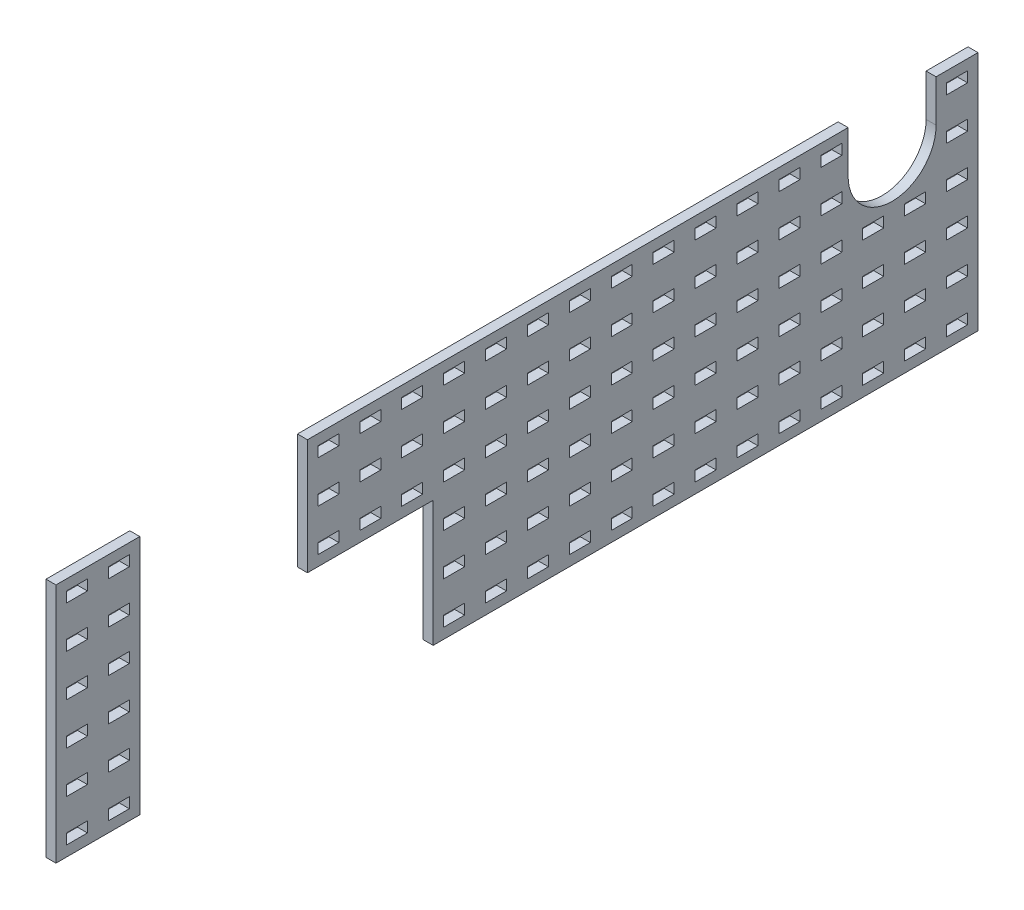
SolidWorks part; units mm, degrees
ref_plane "Front Plane" through (0, 0, 0) normal (0, 0, 1) x (1, 0, 0)
ref_plane "Top Plane" through (0, 0, 0) normal (0, 1, 0) x (1, 0, 0)
ref_plane "Right Plane" through (0, 0, 0) normal (1, 0, 0) x (0, 0, -1)
sketch "Sketch1" plane through (0, 0, 0) normal (1, 0, 0) x (0, 0, -1)
  line L1 (-279.4, -73.025) -> (279.4, -73.025)
  line L2 (-279.4, -73.025) -> (-279.4, 73.025)
  line L3 (-279.4, 73.025) -> (279.4, 73.025)
  line L4 (279.4, -73.025) -> (279.4, 73.025)
  line L5 (-279.4, -73.025) -> (279.4, 73.025) construction
  line L6 (-279.4, 73.025) -> (279.4, -73.025) construction
  point P0 (0, 0)
  dimension "D1" = 558.8
  dimension "D2" = 146.05
extrude "Boss-Extrude1" add sketch "Sketch1" along normal mid plane 6.0452
sketch "Sketch2" plane through (3.0226, 0, 0) normal (1, 0, 0) x (0, 0, -1)
  line L0 (-279.4, -73.025) -> (279.4, -73.025) construction
  line L1 (260.35, -60.325) -> (273.05, -60.325)
  line L2 (260.35, -60.325) -> (260.35, -66.675)
  line L3 (260.35, -66.675) -> (273.05, -66.675)
  line L4 (273.05, -60.325) -> (273.05, -66.675)
  line L5 (260.35, -60.325) -> (273.05, -66.675) construction
  line L6 (260.35, -66.675) -> (273.05, -60.325) construction
  line L7 (279.4, -73.025) -> (279.4, 73.025) construction
  line L8 (234.95, -66.675) -> (247.65, -66.675)
  line L9 (234.95, -60.325) -> (234.95, -66.675)
  line L10 (234.95, -60.325) -> (247.65, -60.325)
  line L11 (247.65, -60.325) -> (247.65, -66.675)
  line L12 (209.55, -66.675) -> (222.25, -66.675)
  line L13 (209.55, -60.325) -> (209.55, -66.675)
  line L14 (209.55, -60.325) -> (222.25, -60.325)
  line L15 (222.25, -60.325) -> (222.25, -66.675)
  line L16 (184.15, -66.675) -> (196.85, -66.675)
  line L17 (184.15, -60.325) -> (184.15, -66.675)
  line L18 (184.15, -60.325) -> (196.85, -60.325)
  line L19 (196.85, -60.325) -> (196.85, -66.675)
  line L20 (158.75, -66.675) -> (171.45, -66.675)
  line L21 (158.75, -60.325) -> (158.75, -66.675)
  line L22 (158.75, -60.325) -> (171.45, -60.325)
  line L23 (171.45, -60.325) -> (171.45, -66.675)
  line L24 (133.35, -66.675) -> (146.05, -66.675)
  line L25 (133.35, -60.325) -> (133.35, -66.675)
  line L26 (133.35, -60.325) -> (146.05, -60.325)
  line L27 (146.05, -60.325) -> (146.05, -66.675)
  line L28 (107.95, -66.675) -> (120.65, -66.675)
  line L29 (107.95, -60.325) -> (107.95, -66.675)
  line L30 (107.95, -60.325) -> (120.65, -60.325)
  line L31 (120.65, -60.325) -> (120.65, -66.675)
  line L32 (82.55, -66.675) -> (95.25, -66.675)
  line L33 (82.55, -60.325) -> (82.55, -66.675)
  line L34 (82.55, -60.325) -> (95.25, -60.325)
  line L35 (95.25, -60.325) -> (95.25, -66.675)
  line L36 (57.15, -66.675) -> (69.85, -66.675)
  line L37 (57.15, -60.325) -> (57.15, -66.675)
  line L38 (57.15, -60.325) -> (69.85, -60.325)
  line L39 (69.85, -60.325) -> (69.85, -66.675)
  line L40 (31.75, -66.675) -> (44.45, -66.675)
  line L41 (31.75, -60.325) -> (31.75, -66.675)
  line L42 (31.75, -60.325) -> (44.45, -60.325)
  line L43 (44.45, -60.325) -> (44.45, -66.675)
  line L44 (6.35, -66.675) -> (19.05, -66.675)
  line L45 (6.35, -60.325) -> (6.35, -66.675)
  line L46 (6.35, -60.325) -> (19.05, -60.325)
  line L47 (19.05, -60.325) -> (19.05, -66.675)
  line L48 (-19.05, -66.675) -> (-6.35, -66.675)
  line L49 (-19.05, -60.325) -> (-19.05, -66.675)
  line L50 (-19.05, -60.325) -> (-6.35, -60.325)
  line L51 (-6.35, -60.325) -> (-6.35, -66.675)
  line L52 (-44.45, -66.675) -> (-31.75, -66.675)
  line L53 (-44.45, -60.325) -> (-44.45, -66.675)
  line L54 (-44.45, -60.325) -> (-31.75, -60.325)
  line L55 (-31.75, -60.325) -> (-31.75, -66.675)
  line L56 (-69.85, -66.675) -> (-57.15, -66.675)
  line L57 (-69.85, -60.325) -> (-69.85, -66.675)
  line L58 (-69.85, -60.325) -> (-57.15, -60.325)
  line L59 (-57.15, -60.325) -> (-57.15, -66.675)
  line L60 (-95.25, -66.675) -> (-82.55, -66.675)
  line L61 (-95.25, -60.325) -> (-95.25, -66.675)
  line L62 (-95.25, -60.325) -> (-82.55, -60.325)
  line L63 (-82.55, -60.325) -> (-82.55, -66.675)
  line L64 (-120.65, -66.675) -> (-107.95, -66.675)
  line L65 (-120.65, -60.325) -> (-120.65, -66.675)
  line L66 (-120.65, -60.325) -> (-107.95, -60.325)
  line L67 (-107.95, -60.325) -> (-107.95, -66.675)
  line L68 (-146.05, -66.675) -> (-133.35, -66.675)
  line L69 (-146.05, -60.325) -> (-146.05, -66.675)
  line L70 (-146.05, -60.325) -> (-133.35, -60.325)
  line L71 (-133.35, -60.325) -> (-133.35, -66.675)
  line L72 (-171.45, -66.675) -> (-158.75, -66.675)
  line L73 (-171.45, -60.325) -> (-171.45, -66.675)
  line L74 (-171.45, -60.325) -> (-158.75, -60.325)
  line L75 (-158.75, -60.325) -> (-158.75, -66.675)
  line L76 (-196.85, -66.675) -> (-184.15, -66.675)
  line L77 (-196.85, -60.325) -> (-196.85, -66.675)
  line L78 (-196.85, -60.325) -> (-184.15, -60.325)
  line L79 (-184.15, -60.325) -> (-184.15, -66.675)
  line L80 (-222.25, -66.675) -> (-209.55, -66.675)
  line L81 (-222.25, -60.325) -> (-222.25, -66.675)
  line L82 (-222.25, -60.325) -> (-209.55, -60.325)
  line L83 (-209.55, -60.325) -> (-209.55, -66.675)
  line L84 (-247.65, -66.675) -> (-234.95, -66.675)
  line L85 (-247.65, -60.325) -> (-247.65, -66.675)
  line L86 (-247.65, -60.325) -> (-234.95, -60.325)
  line L87 (-234.95, -60.325) -> (-234.95, -66.675)
  line L88 (-273.05, -66.675) -> (-260.35, -66.675)
  line L89 (-273.05, -60.325) -> (-273.05, -66.675)
  line L90 (-273.05, -60.325) -> (-260.35, -60.325)
  line L91 (-260.35, -60.325) -> (-260.35, -66.675)
  line L92 (234.95, -41.275) -> (247.65, -41.275)
  line L93 (234.95, -34.925) -> (234.95, -41.275)
  line L94 (234.95, -34.925) -> (247.65, -34.925)
  line L95 (247.65, -34.925) -> (247.65, -41.275)
  line L96 (209.55, -41.275) -> (222.25, -41.275)
  line L97 (209.55, -34.925) -> (209.55, -41.275)
  line L98 (209.55, -34.925) -> (222.25, -34.925)
  line L99 (222.25, -34.925) -> (222.25, -41.275)
  line L100 (184.15, -41.275) -> (196.85, -41.275)
  line L101 (184.15, -34.925) -> (184.15, -41.275)
  line L102 (184.15, -34.925) -> (196.85, -34.925)
  line L103 (196.85, -34.925) -> (196.85, -41.275)
  line L104 (158.75, -41.275) -> (171.45, -41.275)
  line L105 (158.75, -34.925) -> (158.75, -41.275)
  line L106 (158.75, -34.925) -> (171.45, -34.925)
  line L107 (171.45, -34.925) -> (171.45, -41.275)
  line L108 (133.35, -41.275) -> (146.05, -41.275)
  line L109 (133.35, -34.925) -> (133.35, -41.275)
  line L110 (133.35, -34.925) -> (146.05, -34.925)
  line L111 (146.05, -34.925) -> (146.05, -41.275)
  line L112 (107.95, -41.275) -> (120.65, -41.275)
  line L113 (107.95, -34.925) -> (107.95, -41.275)
  line L114 (107.95, -34.925) -> (120.65, -34.925)
  line L115 (120.65, -34.925) -> (120.65, -41.275)
  line L116 (82.55, -41.275) -> (95.25, -41.275)
  line L117 (82.55, -34.925) -> (82.55, -41.275)
  line L118 (82.55, -34.925) -> (95.25, -34.925)
  line L119 (95.25, -34.925) -> (95.25, -41.275)
  line L120 (57.15, -41.275) -> (69.85, -41.275)
  line L121 (57.15, -34.925) -> (57.15, -41.275)
  line L122 (57.15, -34.925) -> (69.85, -34.925)
  line L123 (69.85, -34.925) -> (69.85, -41.275)
  line L124 (31.75, -41.275) -> (44.45, -41.275)
  line L125 (31.75, -34.925) -> (31.75, -41.275)
  line L126 (31.75, -34.925) -> (44.45, -34.925)
  line L127 (44.45, -34.925) -> (44.45, -41.275)
  line L128 (6.35, -41.275) -> (19.05, -41.275)
  line L129 (6.35, -34.925) -> (6.35, -41.275)
  line L130 (6.35, -34.925) -> (19.05, -34.925)
  line L131 (19.05, -34.925) -> (19.05, -41.275)
  line L132 (-19.05, -41.275) -> (-6.35, -41.275)
  line L133 (-19.05, -34.925) -> (-19.05, -41.275)
  line L134 (-19.05, -34.925) -> (-6.35, -34.925)
  line L135 (-6.35, -34.925) -> (-6.35, -41.275)
  line L136 (-44.45, -41.275) -> (-31.75, -41.275)
  line L137 (-44.45, -34.925) -> (-44.45, -41.275)
  line L138 (-44.45, -34.925) -> (-31.75, -34.925)
  line L139 (-31.75, -34.925) -> (-31.75, -41.275)
  line L140 (-69.85, -41.275) -> (-57.15, -41.275)
  line L141 (-69.85, -34.925) -> (-69.85, -41.275)
  line L142 (-69.85, -34.925) -> (-57.15, -34.925)
  line L143 (-57.15, -34.925) -> (-57.15, -41.275)
  line L144 (-95.25, -41.275) -> (-82.55, -41.275)
  line L145 (-95.25, -34.925) -> (-95.25, -41.275)
  line L146 (-95.25, -34.925) -> (-82.55, -34.925)
  line L147 (-82.55, -34.925) -> (-82.55, -41.275)
  line L148 (-120.65, -41.275) -> (-107.95, -41.275)
  line L149 (-120.65, -34.925) -> (-120.65, -41.275)
  line L150 (-120.65, -34.925) -> (-107.95, -34.925)
  line L151 (-107.95, -34.925) -> (-107.95, -41.275)
  line L152 (-146.05, -41.275) -> (-133.35, -41.275)
  line L153 (-146.05, -34.925) -> (-146.05, -41.275)
  line L154 (-146.05, -34.925) -> (-133.35, -34.925)
  line L155 (-133.35, -34.925) -> (-133.35, -41.275)
  line L156 (-171.45, -41.275) -> (-158.75, -41.275)
  line L157 (-171.45, -34.925) -> (-171.45, -41.275)
  line L158 (-171.45, -34.925) -> (-158.75, -34.925)
  line L159 (-158.75, -34.925) -> (-158.75, -41.275)
  line L160 (-196.85, -41.275) -> (-184.15, -41.275)
  line L161 (-196.85, -34.925) -> (-196.85, -41.275)
  line L162 (-196.85, -34.925) -> (-184.15, -34.925)
  line L163 (-184.15, -34.925) -> (-184.15, -41.275)
  line L164 (-222.25, -41.275) -> (-209.55, -41.275)
  line L165 (-222.25, -34.925) -> (-222.25, -41.275)
  line L166 (-222.25, -34.925) -> (-209.55, -34.925)
  line L167 (-209.55, -34.925) -> (-209.55, -41.275)
  line L168 (-247.65, -41.275) -> (-234.95, -41.275)
  line L169 (-247.65, -34.925) -> (-247.65, -41.275)
  line L170 (-247.65, -34.925) -> (-234.95, -34.925)
  line L171 (-234.95, -34.925) -> (-234.95, -41.275)
  line L172 (-273.05, -41.275) -> (-260.35, -41.275)
  line L173 (-273.05, -34.925) -> (-273.05, -41.275)
  line L174 (-273.05, -34.925) -> (-260.35, -34.925)
  line L175 (-260.35, -34.925) -> (-260.35, -41.275)
  line L176 (234.95, -15.875) -> (247.65, -15.875)
  line L177 (234.95, -9.525) -> (234.95, -15.875)
  line L178 (234.95, -9.525) -> (247.65, -9.525)
  line L179 (247.65, -9.525) -> (247.65, -15.875)
  line L180 (209.55, -15.875) -> (222.25, -15.875)
  line L181 (209.55, -9.525) -> (209.55, -15.875)
  line L182 (209.55, -9.525) -> (222.25, -9.525)
  line L183 (222.25, -9.525) -> (222.25, -15.875)
  line L184 (184.15, -15.875) -> (196.85, -15.875)
  line L185 (184.15, -9.525) -> (184.15, -15.875)
  line L186 (184.15, -9.525) -> (196.85, -9.525)
  line L187 (196.85, -9.525) -> (196.85, -15.875)
  line L188 (158.75, -15.875) -> (171.45, -15.875)
  line L189 (158.75, -9.525) -> (158.75, -15.875)
  line L190 (158.75, -9.525) -> (171.45, -9.525)
  line L191 (171.45, -9.525) -> (171.45, -15.875)
  line L192 (133.35, -15.875) -> (146.05, -15.875)
  line L193 (133.35, -9.525) -> (133.35, -15.875)
  line L194 (133.35, -9.525) -> (146.05, -9.525)
  line L195 (146.05, -9.525) -> (146.05, -15.875)
  line L196 (107.95, -15.875) -> (120.65, -15.875)
  line L197 (107.95, -9.525) -> (107.95, -15.875)
  line L198 (107.95, -9.525) -> (120.65, -9.525)
  line L199 (120.65, -9.525) -> (120.65, -15.875)
  line L200 (82.55, -15.875) -> (95.25, -15.875)
  line L201 (82.55, -9.525) -> (82.55, -15.875)
  line L202 (82.55, -9.525) -> (95.25, -9.525)
  line L203 (95.25, -9.525) -> (95.25, -15.875)
  line L204 (57.15, -15.875) -> (69.85, -15.875)
  line L205 (57.15, -9.525) -> (57.15, -15.875)
  line L206 (57.15, -9.525) -> (69.85, -9.525)
  line L207 (69.85, -9.525) -> (69.85, -15.875)
  line L208 (31.75, -15.875) -> (44.45, -15.875)
  line L209 (31.75, -9.525) -> (31.75, -15.875)
  line L210 (31.75, -9.525) -> (44.45, -9.525)
  line L211 (44.45, -9.525) -> (44.45, -15.875)
  line L212 (6.35, -15.875) -> (19.05, -15.875)
  line L213 (6.35, -9.525) -> (6.35, -15.875)
  line L214 (6.35, -9.525) -> (19.05, -9.525)
  line L215 (19.05, -9.525) -> (19.05, -15.875)
  line L216 (-19.05, -15.875) -> (-6.35, -15.875)
  line L217 (-19.05, -9.525) -> (-19.05, -15.875)
  line L218 (-19.05, -9.525) -> (-6.35, -9.525)
  line L219 (-6.35, -9.525) -> (-6.35, -15.875)
  line L220 (-44.45, -15.875) -> (-31.75, -15.875)
  line L221 (-44.45, -9.525) -> (-44.45, -15.875)
  line L222 (-44.45, -9.525) -> (-31.75, -9.525)
  line L223 (-31.75, -9.525) -> (-31.75, -15.875)
  line L224 (-69.85, -15.875) -> (-57.15, -15.875)
  line L225 (-69.85, -9.525) -> (-69.85, -15.875)
  line L226 (-69.85, -9.525) -> (-57.15, -9.525)
  line L227 (-57.15, -9.525) -> (-57.15, -15.875)
  line L228 (-95.25, -15.875) -> (-82.55, -15.875)
  line L229 (-95.25, -9.525) -> (-95.25, -15.875)
  line L230 (-95.25, -9.525) -> (-82.55, -9.525)
  line L231 (-82.55, -9.525) -> (-82.55, -15.875)
  line L232 (-120.65, -15.875) -> (-107.95, -15.875)
  line L233 (-120.65, -9.525) -> (-120.65, -15.875)
  line L234 (-120.65, -9.525) -> (-107.95, -9.525)
  line L235 (-107.95, -9.525) -> (-107.95, -15.875)
  line L236 (-146.05, -15.875) -> (-133.35, -15.875)
  line L237 (-146.05, -9.525) -> (-146.05, -15.875)
  line L238 (-146.05, -9.525) -> (-133.35, -9.525)
  line L239 (-133.35, -9.525) -> (-133.35, -15.875)
  line L240 (-171.45, -15.875) -> (-158.75, -15.875)
  line L241 (-171.45, -9.525) -> (-171.45, -15.875)
  line L242 (-171.45, -9.525) -> (-158.75, -9.525)
  line L243 (-158.75, -9.525) -> (-158.75, -15.875)
  line L244 (-196.85, -15.875) -> (-184.15, -15.875)
  line L245 (-196.85, -9.525) -> (-196.85, -15.875)
  line L246 (-196.85, -9.525) -> (-184.15, -9.525)
  line L247 (-184.15, -9.525) -> (-184.15, -15.875)
  line L248 (-222.25, -15.875) -> (-209.55, -15.875)
  line L249 (-222.25, -9.525) -> (-222.25, -15.875)
  line L250 (-222.25, -9.525) -> (-209.55, -9.525)
  line L251 (-209.55, -9.525) -> (-209.55, -15.875)
  line L252 (-247.65, -15.875) -> (-234.95, -15.875)
  line L253 (-247.65, -9.525) -> (-247.65, -15.875)
  line L254 (-247.65, -9.525) -> (-234.95, -9.525)
  line L255 (-234.95, -9.525) -> (-234.95, -15.875)
  line L256 (-273.05, -15.875) -> (-260.35, -15.875)
  line L257 (-273.05, -9.525) -> (-273.05, -15.875)
  line L258 (-273.05, -9.525) -> (-260.35, -9.525)
  line L259 (-260.35, -9.525) -> (-260.35, -15.875)
  line L260 (234.95, 9.525) -> (247.65, 9.525)
  line L261 (234.95, 15.875) -> (234.95, 9.525)
  line L262 (234.95, 15.875) -> (247.65, 15.875)
  line L263 (247.65, 15.875) -> (247.65, 9.525)
  line L264 (209.55, 9.525) -> (222.25, 9.525)
  line L265 (209.55, 15.875) -> (209.55, 9.525)
  line L266 (209.55, 15.875) -> (222.25, 15.875)
  line L267 (222.25, 15.875) -> (222.25, 9.525)
  line L268 (184.15, 9.525) -> (196.85, 9.525)
  line L269 (184.15, 15.875) -> (184.15, 9.525)
  line L270 (184.15, 15.875) -> (196.85, 15.875)
  line L271 (196.85, 15.875) -> (196.85, 9.525)
  line L272 (158.75, 9.525) -> (171.45, 9.525)
  line L273 (158.75, 15.875) -> (158.75, 9.525)
  line L274 (158.75, 15.875) -> (171.45, 15.875)
  line L275 (171.45, 15.875) -> (171.45, 9.525)
  line L276 (133.35, 9.525) -> (146.05, 9.525)
  line L277 (133.35, 15.875) -> (133.35, 9.525)
  line L278 (133.35, 15.875) -> (146.05, 15.875)
  line L279 (146.05, 15.875) -> (146.05, 9.525)
  line L280 (107.95, 9.525) -> (120.65, 9.525)
  line L281 (107.95, 15.875) -> (107.95, 9.525)
  line L282 (107.95, 15.875) -> (120.65, 15.875)
  line L283 (120.65, 15.875) -> (120.65, 9.525)
  line L284 (82.55, 9.525) -> (95.25, 9.525)
  line L285 (82.55, 15.875) -> (82.55, 9.525)
  line L286 (82.55, 15.875) -> (95.25, 15.875)
  line L287 (95.25, 15.875) -> (95.25, 9.525)
  line L288 (57.15, 9.525) -> (69.85, 9.525)
  line L289 (57.15, 15.875) -> (57.15, 9.525)
  line L290 (57.15, 15.875) -> (69.85, 15.875)
  line L291 (69.85, 15.875) -> (69.85, 9.525)
  line L292 (31.75, 9.525) -> (44.45, 9.525)
  line L293 (31.75, 15.875) -> (31.75, 9.525)
  line L294 (31.75, 15.875) -> (44.45, 15.875)
  line L295 (44.45, 15.875) -> (44.45, 9.525)
  line L296 (6.35, 9.525) -> (19.05, 9.525)
  line L297 (6.35, 15.875) -> (6.35, 9.525)
  line L298 (6.35, 15.875) -> (19.05, 15.875)
  line L299 (19.05, 15.875) -> (19.05, 9.525)
  line L300 (-19.05, 9.525) -> (-6.35, 9.525)
  line L301 (-19.05, 15.875) -> (-19.05, 9.525)
  line L302 (-19.05, 15.875) -> (-6.35, 15.875)
  line L303 (-6.35, 15.875) -> (-6.35, 9.525)
  line L304 (-44.45, 9.525) -> (-31.75, 9.525)
  line L305 (-44.45, 15.875) -> (-44.45, 9.525)
  line L306 (-44.45, 15.875) -> (-31.75, 15.875)
  line L307 (-31.75, 15.875) -> (-31.75, 9.525)
  line L308 (-69.85, 9.525) -> (-57.15, 9.525)
  line L309 (-69.85, 15.875) -> (-69.85, 9.525)
  line L310 (-69.85, 15.875) -> (-57.15, 15.875)
  line L311 (-57.15, 15.875) -> (-57.15, 9.525)
  line L312 (-95.25, 9.525) -> (-82.55, 9.525)
  line L313 (-95.25, 15.875) -> (-95.25, 9.525)
  line L314 (-95.25, 15.875) -> (-82.55, 15.875)
  line L315 (-82.55, 15.875) -> (-82.55, 9.525)
  line L316 (-120.65, 9.525) -> (-107.95, 9.525)
  line L317 (-120.65, 15.875) -> (-120.65, 9.525)
  line L318 (-120.65, 15.875) -> (-107.95, 15.875)
  line L319 (-107.95, 15.875) -> (-107.95, 9.525)
  line L320 (-146.05, 9.525) -> (-133.35, 9.525)
  line L321 (-146.05, 15.875) -> (-146.05, 9.525)
  line L322 (-146.05, 15.875) -> (-133.35, 15.875)
  line L323 (-133.35, 15.875) -> (-133.35, 9.525)
  line L324 (-171.45, 9.525) -> (-158.75, 9.525)
  line L325 (-171.45, 15.875) -> (-171.45, 9.525)
  line L326 (-171.45, 15.875) -> (-158.75, 15.875)
  line L327 (-158.75, 15.875) -> (-158.75, 9.525)
  line L328 (-196.85, 9.525) -> (-184.15, 9.525)
  line L329 (-196.85, 15.875) -> (-196.85, 9.525)
  line L330 (-196.85, 15.875) -> (-184.15, 15.875)
  line L331 (-184.15, 15.875) -> (-184.15, 9.525)
  line L332 (-222.25, 9.525) -> (-209.55, 9.525)
  line L333 (-222.25, 15.875) -> (-222.25, 9.525)
  line L334 (-222.25, 15.875) -> (-209.55, 15.875)
  line L335 (-209.55, 15.875) -> (-209.55, 9.525)
  line L336 (-247.65, 9.525) -> (-234.95, 9.525)
  line L337 (-247.65, 15.875) -> (-247.65, 9.525)
  line L338 (-247.65, 15.875) -> (-234.95, 15.875)
  line L339 (-234.95, 15.875) -> (-234.95, 9.525)
  line L340 (-273.05, 9.525) -> (-260.35, 9.525)
  line L341 (-273.05, 15.875) -> (-273.05, 9.525)
  line L342 (-273.05, 15.875) -> (-260.35, 15.875)
  line L343 (-260.35, 15.875) -> (-260.35, 9.525)
  line L344 (234.95, 34.925) -> (247.65, 34.925)
  line L345 (234.95, 41.275) -> (234.95, 34.925)
  line L346 (234.95, 41.275) -> (247.65, 41.275)
  line L347 (247.65, 41.275) -> (247.65, 34.925)
  line L348 (209.55, 34.925) -> (222.25, 34.925)
  line L349 (209.55, 41.275) -> (209.55, 34.925)
  line L350 (209.55, 41.275) -> (222.25, 41.275)
  line L351 (222.25, 41.275) -> (222.25, 34.925)
  line L352 (184.15, 34.925) -> (196.85, 34.925)
  line L353 (184.15, 41.275) -> (184.15, 34.925)
  line L354 (184.15, 41.275) -> (196.85, 41.275)
  line L355 (196.85, 41.275) -> (196.85, 34.925)
  line L356 (158.75, 34.925) -> (171.45, 34.925)
  line L357 (158.75, 41.275) -> (158.75, 34.925)
  line L358 (158.75, 41.275) -> (171.45, 41.275)
  line L359 (171.45, 41.275) -> (171.45, 34.925)
  line L360 (133.35, 34.925) -> (146.05, 34.925)
  line L361 (133.35, 41.275) -> (133.35, 34.925)
  line L362 (133.35, 41.275) -> (146.05, 41.275)
  line L363 (146.05, 41.275) -> (146.05, 34.925)
  line L364 (107.95, 34.925) -> (120.65, 34.925)
  line L365 (107.95, 41.275) -> (107.95, 34.925)
  line L366 (107.95, 41.275) -> (120.65, 41.275)
  line L367 (120.65, 41.275) -> (120.65, 34.925)
  line L368 (82.55, 34.925) -> (95.25, 34.925)
  line L369 (82.55, 41.275) -> (82.55, 34.925)
  line L370 (82.55, 41.275) -> (95.25, 41.275)
  line L371 (95.25, 41.275) -> (95.25, 34.925)
  line L372 (57.15, 34.925) -> (69.85, 34.925)
  line L373 (57.15, 41.275) -> (57.15, 34.925)
  line L374 (57.15, 41.275) -> (69.85, 41.275)
  line L375 (69.85, 41.275) -> (69.85, 34.925)
  line L376 (31.75, 34.925) -> (44.45, 34.925)
  line L377 (31.75, 41.275) -> (31.75, 34.925)
  line L378 (31.75, 41.275) -> (44.45, 41.275)
  line L379 (44.45, 41.275) -> (44.45, 34.925)
  line L380 (6.35, 34.925) -> (19.05, 34.925)
  line L381 (6.35, 41.275) -> (6.35, 34.925)
  line L382 (6.35, 41.275) -> (19.05, 41.275)
  line L383 (19.05, 41.275) -> (19.05, 34.925)
  line L384 (-19.05, 34.925) -> (-6.35, 34.925)
  line L385 (-19.05, 41.275) -> (-19.05, 34.925)
  line L386 (-19.05, 41.275) -> (-6.35, 41.275)
  line L387 (-6.35, 41.275) -> (-6.35, 34.925)
  line L388 (-44.45, 34.925) -> (-31.75, 34.925)
  line L389 (-44.45, 41.275) -> (-44.45, 34.925)
  line L390 (-44.45, 41.275) -> (-31.75, 41.275)
  line L391 (-31.75, 41.275) -> (-31.75, 34.925)
  line L392 (-69.85, 34.925) -> (-57.15, 34.925)
  line L393 (-69.85, 41.275) -> (-69.85, 34.925)
  line L394 (-69.85, 41.275) -> (-57.15, 41.275)
  line L395 (-57.15, 41.275) -> (-57.15, 34.925)
  line L396 (-95.25, 34.925) -> (-82.55, 34.925)
  line L397 (-95.25, 41.275) -> (-95.25, 34.925)
  line L398 (-95.25, 41.275) -> (-82.55, 41.275)
  line L399 (-82.55, 41.275) -> (-82.55, 34.925)
  line L400 (-120.65, 34.925) -> (-107.95, 34.925)
  line L401 (-120.65, 41.275) -> (-120.65, 34.925)
  line L402 (-120.65, 41.275) -> (-107.95, 41.275)
  line L403 (-107.95, 41.275) -> (-107.95, 34.925)
  line L404 (-146.05, 34.925) -> (-133.35, 34.925)
  line L405 (-146.05, 41.275) -> (-146.05, 34.925)
  line L406 (-146.05, 41.275) -> (-133.35, 41.275)
  line L407 (-133.35, 41.275) -> (-133.35, 34.925)
  line L408 (-171.45, 34.925) -> (-158.75, 34.925)
  line L409 (-171.45, 41.275) -> (-171.45, 34.925)
  line L410 (-171.45, 41.275) -> (-158.75, 41.275)
  line L411 (-158.75, 41.275) -> (-158.75, 34.925)
  line L412 (-196.85, 34.925) -> (-184.15, 34.925)
  line L413 (-196.85, 41.275) -> (-196.85, 34.925)
  line L414 (-196.85, 41.275) -> (-184.15, 41.275)
  line L415 (-184.15, 41.275) -> (-184.15, 34.925)
  line L416 (-222.25, 34.925) -> (-209.55, 34.925)
  line L417 (-222.25, 41.275) -> (-222.25, 34.925)
  line L418 (-222.25, 41.275) -> (-209.55, 41.275)
  line L419 (-209.55, 41.275) -> (-209.55, 34.925)
  line L420 (-247.65, 34.925) -> (-234.95, 34.925)
  line L421 (-247.65, 41.275) -> (-247.65, 34.925)
  line L422 (-247.65, 41.275) -> (-234.95, 41.275)
  line L423 (-234.95, 41.275) -> (-234.95, 34.925)
  line L424 (-273.05, 34.925) -> (-260.35, 34.925)
  line L425 (-273.05, 41.275) -> (-273.05, 34.925)
  line L426 (-273.05, 41.275) -> (-260.35, 41.275)
  line L427 (-260.35, 41.275) -> (-260.35, 34.925)
  line L428 (234.95, 60.325) -> (247.65, 60.325)
  line L429 (234.95, 66.675) -> (234.95, 60.325)
  line L430 (234.95, 66.675) -> (247.65, 66.675)
  line L431 (247.65, 66.675) -> (247.65, 60.325)
  line L432 (209.55, 60.325) -> (222.25, 60.325)
  line L433 (209.55, 66.675) -> (209.55, 60.325)
  line L434 (209.55, 66.675) -> (222.25, 66.675)
  line L435 (222.25, 66.675) -> (222.25, 60.325)
  line L436 (184.15, 60.325) -> (196.85, 60.325)
  line L437 (184.15, 66.675) -> (184.15, 60.325)
  line L438 (184.15, 66.675) -> (196.85, 66.675)
  line L439 (196.85, 66.675) -> (196.85, 60.325)
  line L440 (158.75, 60.325) -> (171.45, 60.325)
  line L441 (158.75, 66.675) -> (158.75, 60.325)
  line L442 (158.75, 66.675) -> (171.45, 66.675)
  line L443 (171.45, 66.675) -> (171.45, 60.325)
  line L444 (133.35, 60.325) -> (146.05, 60.325)
  line L445 (133.35, 66.675) -> (133.35, 60.325)
  line L446 (133.35, 66.675) -> (146.05, 66.675)
  line L447 (146.05, 66.675) -> (146.05, 60.325)
  line L448 (107.95, 60.325) -> (120.65, 60.325)
  line L449 (107.95, 66.675) -> (107.95, 60.325)
  line L450 (107.95, 66.675) -> (120.65, 66.675)
  line L451 (120.65, 66.675) -> (120.65, 60.325)
  line L452 (82.55, 60.325) -> (95.25, 60.325)
  line L453 (82.55, 66.675) -> (82.55, 60.325)
  line L454 (82.55, 66.675) -> (95.25, 66.675)
  line L455 (95.25, 66.675) -> (95.25, 60.325)
  line L456 (57.15, 60.325) -> (69.85, 60.325)
  line L457 (57.15, 66.675) -> (57.15, 60.325)
  line L458 (57.15, 66.675) -> (69.85, 66.675)
  line L459 (69.85, 66.675) -> (69.85, 60.325)
  line L460 (31.75, 60.325) -> (44.45, 60.325)
  line L461 (31.75, 66.675) -> (31.75, 60.325)
  line L462 (31.75, 66.675) -> (44.45, 66.675)
  line L463 (44.45, 66.675) -> (44.45, 60.325)
  line L464 (6.35, 60.325) -> (19.05, 60.325)
  line L465 (6.35, 66.675) -> (6.35, 60.325)
  line L466 (6.35, 66.675) -> (19.05, 66.675)
  line L467 (19.05, 66.675) -> (19.05, 60.325)
  line L468 (-19.05, 60.325) -> (-6.35, 60.325)
  line L469 (-19.05, 66.675) -> (-19.05, 60.325)
  line L470 (-19.05, 66.675) -> (-6.35, 66.675)
  line L471 (-6.35, 66.675) -> (-6.35, 60.325)
  line L472 (-44.45, 60.325) -> (-31.75, 60.325)
  line L473 (-44.45, 66.675) -> (-44.45, 60.325)
  line L474 (-44.45, 66.675) -> (-31.75, 66.675)
  line L475 (-31.75, 66.675) -> (-31.75, 60.325)
  line L476 (-69.85, 60.325) -> (-57.15, 60.325)
  line L477 (-69.85, 66.675) -> (-69.85, 60.325)
  line L478 (-69.85, 66.675) -> (-57.15, 66.675)
  line L479 (-57.15, 66.675) -> (-57.15, 60.325)
  line L480 (-95.25, 60.325) -> (-82.55, 60.325)
  line L481 (-95.25, 66.675) -> (-95.25, 60.325)
  line L482 (-95.25, 66.675) -> (-82.55, 66.675)
  line L483 (-82.55, 66.675) -> (-82.55, 60.325)
  line L484 (-120.65, 60.325) -> (-107.95, 60.325)
  line L485 (-120.65, 66.675) -> (-120.65, 60.325)
  line L486 (-120.65, 66.675) -> (-107.95, 66.675)
  line L487 (-107.95, 66.675) -> (-107.95, 60.325)
  line L488 (-146.05, 60.325) -> (-133.35, 60.325)
  line L489 (-146.05, 66.675) -> (-146.05, 60.325)
  line L490 (-146.05, 66.675) -> (-133.35, 66.675)
  line L491 (-133.35, 66.675) -> (-133.35, 60.325)
  line L492 (-171.45, 60.325) -> (-158.75, 60.325)
  line L493 (-171.45, 66.675) -> (-171.45, 60.325)
  line L494 (-171.45, 66.675) -> (-158.75, 66.675)
  line L495 (-158.75, 66.675) -> (-158.75, 60.325)
  line L496 (-196.85, 60.325) -> (-184.15, 60.325)
  line L497 (-196.85, 66.675) -> (-196.85, 60.325)
  line L498 (-196.85, 66.675) -> (-184.15, 66.675)
  line L499 (-184.15, 66.675) -> (-184.15, 60.325)
  line L500 (-222.25, 60.325) -> (-209.55, 60.325)
  line L501 (-222.25, 66.675) -> (-222.25, 60.325)
  line L502 (-222.25, 66.675) -> (-209.55, 66.675)
  line L503 (-209.55, 66.675) -> (-209.55, 60.325)
  line L504 (-247.65, 60.325) -> (-234.95, 60.325)
  line L505 (-247.65, 66.675) -> (-247.65, 60.325)
  line L506 (-247.65, 66.675) -> (-234.95, 66.675)
  line L507 (-234.95, 66.675) -> (-234.95, 60.325)
  line L508 (-273.05, 60.325) -> (-260.35, 60.325)
  line L509 (-273.05, 66.675) -> (-273.05, 60.325)
  line L510 (-273.05, 66.675) -> (-260.35, 66.675)
  line L511 (-260.35, 66.675) -> (-260.35, 60.325)
  line L512 (234.95, 85.725) -> (247.65, 85.725)
  line L513 (234.95, 92.075) -> (234.95, 85.725)
  line L514 (234.95, 92.075) -> (247.65, 92.075)
  line L515 (247.65, 92.075) -> (247.65, 85.725)
  line L516 (209.55, 85.725) -> (222.25, 85.725)
  line L517 (209.55, 92.075) -> (209.55, 85.725)
  line L518 (209.55, 92.075) -> (222.25, 92.075)
  line L519 (222.25, 92.075) -> (222.25, 85.725)
  line L520 (184.15, 85.725) -> (196.85, 85.725)
  line L521 (184.15, 92.075) -> (184.15, 85.725)
  line L522 (184.15, 92.075) -> (196.85, 92.075)
  line L523 (196.85, 92.075) -> (196.85, 85.725)
  line L524 (158.75, 85.725) -> (171.45, 85.725)
  line L525 (158.75, 92.075) -> (158.75, 85.725)
  line L526 (158.75, 92.075) -> (171.45, 92.075)
  line L527 (171.45, 92.075) -> (171.45, 85.725)
  line L528 (133.35, 85.725) -> (146.05, 85.725)
  line L529 (133.35, 92.075) -> (133.35, 85.725)
  line L530 (133.35, 92.075) -> (146.05, 92.075)
  line L531 (146.05, 92.075) -> (146.05, 85.725)
  line L532 (107.95, 85.725) -> (120.65, 85.725)
  line L533 (107.95, 92.075) -> (107.95, 85.725)
  line L534 (107.95, 92.075) -> (120.65, 92.075)
  line L535 (120.65, 92.075) -> (120.65, 85.725)
  line L536 (82.55, 85.725) -> (95.25, 85.725)
  line L537 (82.55, 92.075) -> (82.55, 85.725)
  line L538 (82.55, 92.075) -> (95.25, 92.075)
  line L539 (95.25, 92.075) -> (95.25, 85.725)
  line L540 (57.15, 85.725) -> (69.85, 85.725)
  line L541 (57.15, 92.075) -> (57.15, 85.725)
  line L542 (57.15, 92.075) -> (69.85, 92.075)
  line L543 (69.85, 92.075) -> (69.85, 85.725)
  line L544 (31.75, 85.725) -> (44.45, 85.725)
  line L545 (31.75, 92.075) -> (31.75, 85.725)
  line L546 (31.75, 92.075) -> (44.45, 92.075)
  line L547 (44.45, 92.075) -> (44.45, 85.725)
  line L548 (6.35, 85.725) -> (19.05, 85.725)
  line L549 (6.35, 92.075) -> (6.35, 85.725)
  line L550 (6.35, 92.075) -> (19.05, 92.075)
  line L551 (19.05, 92.075) -> (19.05, 85.725)
  line L552 (-19.05, 85.725) -> (-6.35, 85.725)
  line L553 (-19.05, 92.075) -> (-19.05, 85.725)
  line L554 (-19.05, 92.075) -> (-6.35, 92.075)
  line L555 (-6.35, 92.075) -> (-6.35, 85.725)
  line L556 (-44.45, 85.725) -> (-31.75, 85.725)
  line L557 (-44.45, 92.075) -> (-44.45, 85.725)
  line L558 (-44.45, 92.075) -> (-31.75, 92.075)
  line L559 (-31.75, 92.075) -> (-31.75, 85.725)
  line L560 (-69.85, 85.725) -> (-57.15, 85.725)
  line L561 (-69.85, 92.075) -> (-69.85, 85.725)
  line L562 (-69.85, 92.075) -> (-57.15, 92.075)
  line L563 (-57.15, 92.075) -> (-57.15, 85.725)
  line L564 (-95.25, 85.725) -> (-82.55, 85.725)
  line L565 (-95.25, 92.075) -> (-95.25, 85.725)
  line L566 (-95.25, 92.075) -> (-82.55, 92.075)
  line L567 (-82.55, 92.075) -> (-82.55, 85.725)
  line L568 (-120.65, 85.725) -> (-107.95, 85.725)
  line L569 (-120.65, 92.075) -> (-120.65, 85.725)
  line L570 (-120.65, 92.075) -> (-107.95, 92.075)
  line L571 (-107.95, 92.075) -> (-107.95, 85.725)
  line L572 (-146.05, 85.725) -> (-133.35, 85.725)
  line L573 (-146.05, 92.075) -> (-146.05, 85.725)
  line L574 (-146.05, 92.075) -> (-133.35, 92.075)
  line L575 (-133.35, 92.075) -> (-133.35, 85.725)
  line L576 (-171.45, 85.725) -> (-158.75, 85.725)
  line L577 (-171.45, 92.075) -> (-171.45, 85.725)
  line L578 (-171.45, 92.075) -> (-158.75, 92.075)
  line L579 (-158.75, 92.075) -> (-158.75, 85.725)
  line L580 (-196.85, 85.725) -> (-184.15, 85.725)
  line L581 (-196.85, 92.075) -> (-196.85, 85.725)
  line L582 (-196.85, 92.075) -> (-184.15, 92.075)
  line L583 (-184.15, 92.075) -> (-184.15, 85.725)
  line L584 (-222.25, 85.725) -> (-209.55, 85.725)
  line L585 (-222.25, 92.075) -> (-222.25, 85.725)
  line L586 (-222.25, 92.075) -> (-209.55, 92.075)
  line L587 (-209.55, 92.075) -> (-209.55, 85.725)
  line L588 (-247.65, 85.725) -> (-234.95, 85.725)
  line L589 (-247.65, 92.075) -> (-247.65, 85.725)
  line L590 (-247.65, 92.075) -> (-234.95, 92.075)
  line L591 (-234.95, 92.075) -> (-234.95, 85.725)
  line L592 (-273.05, 85.725) -> (-260.35, 85.725)
  line L593 (-273.05, 92.075) -> (-273.05, 85.725)
  line L594 (-273.05, 92.075) -> (-260.35, 92.075)
  line L595 (-260.35, 92.075) -> (-260.35, 85.725)
  line L596 (234.95, 111.125) -> (247.65, 111.125)
  line L597 (234.95, 117.475) -> (234.95, 111.125)
  line L598 (234.95, 117.475) -> (247.65, 117.475)
  line L599 (247.65, 117.475) -> (247.65, 111.125)
  line L600 (209.55, 111.125) -> (222.25, 111.125)
  line L601 (209.55, 117.475) -> (209.55, 111.125)
  line L602 (209.55, 117.475) -> (222.25, 117.475)
  line L603 (222.25, 117.475) -> (222.25, 111.125)
  line L604 (184.15, 111.125) -> (196.85, 111.125)
  line L605 (184.15, 117.475) -> (184.15, 111.125)
  line L606 (184.15, 117.475) -> (196.85, 117.475)
  line L607 (196.85, 117.475) -> (196.85, 111.125)
  line L608 (158.75, 111.125) -> (171.45, 111.125)
  line L609 (158.75, 117.475) -> (158.75, 111.125)
  line L610 (158.75, 117.475) -> (171.45, 117.475)
  line L611 (171.45, 117.475) -> (171.45, 111.125)
  line L612 (133.35, 111.125) -> (146.05, 111.125)
  line L613 (133.35, 117.475) -> (133.35, 111.125)
  line L614 (133.35, 117.475) -> (146.05, 117.475)
  line L615 (146.05, 117.475) -> (146.05, 111.125)
  line L616 (107.95, 111.125) -> (120.65, 111.125)
  line L617 (107.95, 117.475) -> (107.95, 111.125)
  line L618 (107.95, 117.475) -> (120.65, 117.475)
  line L619 (120.65, 117.475) -> (120.65, 111.125)
  line L620 (82.55, 111.125) -> (95.25, 111.125)
  line L621 (82.55, 117.475) -> (82.55, 111.125)
  line L622 (82.55, 117.475) -> (95.25, 117.475)
  line L623 (95.25, 117.475) -> (95.25, 111.125)
  line L624 (57.15, 111.125) -> (69.85, 111.125)
  line L625 (57.15, 117.475) -> (57.15, 111.125)
  line L626 (57.15, 117.475) -> (69.85, 117.475)
  line L627 (69.85, 117.475) -> (69.85, 111.125)
  line L628 (31.75, 111.125) -> (44.45, 111.125)
  line L629 (31.75, 117.475) -> (31.75, 111.125)
  line L630 (31.75, 117.475) -> (44.45, 117.475)
  line L631 (44.45, 117.475) -> (44.45, 111.125)
  line L632 (6.35, 111.125) -> (19.05, 111.125)
  line L633 (6.35, 117.475) -> (6.35, 111.125)
  line L634 (6.35, 117.475) -> (19.05, 117.475)
  line L635 (19.05, 117.475) -> (19.05, 111.125)
  line L636 (-19.05, 111.125) -> (-6.35, 111.125)
  line L637 (-19.05, 117.475) -> (-19.05, 111.125)
  line L638 (-19.05, 117.475) -> (-6.35, 117.475)
  line L639 (-6.35, 117.475) -> (-6.35, 111.125)
  line L640 (-44.45, 111.125) -> (-31.75, 111.125)
  line L641 (-44.45, 117.475) -> (-44.45, 111.125)
  line L642 (-44.45, 117.475) -> (-31.75, 117.475)
  line L643 (-31.75, 117.475) -> (-31.75, 111.125)
  line L644 (-69.85, 111.125) -> (-57.15, 111.125)
  line L645 (-69.85, 117.475) -> (-69.85, 111.125)
  line L646 (-69.85, 117.475) -> (-57.15, 117.475)
  line L647 (-57.15, 117.475) -> (-57.15, 111.125)
  line L648 (-95.25, 111.125) -> (-82.55, 111.125)
  line L649 (-95.25, 117.475) -> (-95.25, 111.125)
  line L650 (-95.25, 117.475) -> (-82.55, 117.475)
  line L651 (-82.55, 117.475) -> (-82.55, 111.125)
  line L652 (-120.65, 111.125) -> (-107.95, 111.125)
  line L653 (-120.65, 117.475) -> (-120.65, 111.125)
  line L654 (-120.65, 117.475) -> (-107.95, 117.475)
  line L655 (-107.95, 117.475) -> (-107.95, 111.125)
  line L656 (-146.05, 111.125) -> (-133.35, 111.125)
  line L657 (-146.05, 117.475) -> (-146.05, 111.125)
  line L658 (-146.05, 117.475) -> (-133.35, 117.475)
  line L659 (-133.35, 117.475) -> (-133.35, 111.125)
  line L660 (-171.45, 111.125) -> (-158.75, 111.125)
  line L661 (-171.45, 117.475) -> (-171.45, 111.125)
  line L662 (-171.45, 117.475) -> (-158.75, 117.475)
  line L663 (-158.75, 117.475) -> (-158.75, 111.125)
  line L664 (-196.85, 111.125) -> (-184.15, 111.125)
  line L665 (-196.85, 117.475) -> (-196.85, 111.125)
  line L666 (-196.85, 117.475) -> (-184.15, 117.475)
  line L667 (-184.15, 117.475) -> (-184.15, 111.125)
  line L668 (-222.25, 111.125) -> (-209.55, 111.125)
  line L669 (-222.25, 117.475) -> (-222.25, 111.125)
  line L670 (-222.25, 117.475) -> (-209.55, 117.475)
  line L671 (-209.55, 117.475) -> (-209.55, 111.125)
  line L672 (-247.65, 111.125) -> (-234.95, 111.125)
  line L673 (-247.65, 117.475) -> (-247.65, 111.125)
  line L674 (-247.65, 117.475) -> (-234.95, 117.475)
  line L675 (-234.95, 117.475) -> (-234.95, 111.125)
  line L676 (-273.05, 111.125) -> (-260.35, 111.125)
  line L677 (-273.05, 117.475) -> (-273.05, 111.125)
  line L678 (-273.05, 117.475) -> (-260.35, 117.475)
  line L679 (-260.35, 117.475) -> (-260.35, 111.125)
  line L680 (234.95, 136.525) -> (247.65, 136.525)
  line L681 (234.95, 142.875) -> (234.95, 136.525)
  line L682 (234.95, 142.875) -> (247.65, 142.875)
  line L683 (247.65, 142.875) -> (247.65, 136.525)
  line L684 (209.55, 136.525) -> (222.25, 136.525)
  line L685 (209.55, 142.875) -> (209.55, 136.525)
  line L686 (209.55, 142.875) -> (222.25, 142.875)
  line L687 (222.25, 142.875) -> (222.25, 136.525)
  line L688 (184.15, 136.525) -> (196.85, 136.525)
  line L689 (184.15, 142.875) -> (184.15, 136.525)
  line L690 (184.15, 142.875) -> (196.85, 142.875)
  line L691 (196.85, 142.875) -> (196.85, 136.525)
  line L692 (158.75, 136.525) -> (171.45, 136.525)
  line L693 (158.75, 142.875) -> (158.75, 136.525)
  line L694 (158.75, 142.875) -> (171.45, 142.875)
  line L695 (171.45, 142.875) -> (171.45, 136.525)
  line L696 (133.35, 136.525) -> (146.05, 136.525)
  line L697 (133.35, 142.875) -> (133.35, 136.525)
  line L698 (133.35, 142.875) -> (146.05, 142.875)
  line L699 (146.05, 142.875) -> (146.05, 136.525)
  line L700 (107.95, 136.525) -> (120.65, 136.525)
  line L701 (107.95, 142.875) -> (107.95, 136.525)
  line L702 (107.95, 142.875) -> (120.65, 142.875)
  line L703 (120.65, 142.875) -> (120.65, 136.525)
  line L704 (82.55, 136.525) -> (95.25, 136.525)
  line L705 (82.55, 142.875) -> (82.55, 136.525)
  line L706 (82.55, 142.875) -> (95.25, 142.875)
  line L707 (95.25, 142.875) -> (95.25, 136.525)
  line L708 (57.15, 136.525) -> (69.85, 136.525)
  line L709 (57.15, 142.875) -> (57.15, 136.525)
  line L710 (57.15, 142.875) -> (69.85, 142.875)
  line L711 (69.85, 142.875) -> (69.85, 136.525)
  line L712 (31.75, 136.525) -> (44.45, 136.525)
  line L713 (31.75, 142.875) -> (31.75, 136.525)
  line L714 (31.75, 142.875) -> (44.45, 142.875)
  line L715 (44.45, 142.875) -> (44.45, 136.525)
  line L716 (6.35, 136.525) -> (19.05, 136.525)
  line L717 (6.35, 142.875) -> (6.35, 136.525)
  line L718 (6.35, 142.875) -> (19.05, 142.875)
  line L719 (19.05, 142.875) -> (19.05, 136.525)
  line L720 (-19.05, 136.525) -> (-6.35, 136.525)
  line L721 (-19.05, 142.875) -> (-19.05, 136.525)
  line L722 (-19.05, 142.875) -> (-6.35, 142.875)
  line L723 (-6.35, 142.875) -> (-6.35, 136.525)
  line L724 (-44.45, 136.525) -> (-31.75, 136.525)
  line L725 (-44.45, 142.875) -> (-44.45, 136.525)
  line L726 (-44.45, 142.875) -> (-31.75, 142.875)
  line L727 (-31.75, 142.875) -> (-31.75, 136.525)
  line L728 (-69.85, 136.525) -> (-57.15, 136.525)
  line L729 (-69.85, 142.875) -> (-69.85, 136.525)
  line L730 (-69.85, 142.875) -> (-57.15, 142.875)
  line L731 (-57.15, 142.875) -> (-57.15, 136.525)
  line L732 (-95.25, 136.525) -> (-82.55, 136.525)
  line L733 (-95.25, 142.875) -> (-95.25, 136.525)
  line L734 (-95.25, 142.875) -> (-82.55, 142.875)
  line L735 (-82.55, 142.875) -> (-82.55, 136.525)
  line L736 (-120.65, 136.525) -> (-107.95, 136.525)
  line L737 (-120.65, 142.875) -> (-120.65, 136.525)
  line L738 (-120.65, 142.875) -> (-107.95, 142.875)
  line L739 (-107.95, 142.875) -> (-107.95, 136.525)
  line L740 (-146.05, 136.525) -> (-133.35, 136.525)
  line L741 (-146.05, 142.875) -> (-146.05, 136.525)
  line L742 (-146.05, 142.875) -> (-133.35, 142.875)
  line L743 (-133.35, 142.875) -> (-133.35, 136.525)
  line L744 (-171.45, 136.525) -> (-158.75, 136.525)
  line L745 (-171.45, 142.875) -> (-171.45, 136.525)
  line L746 (-171.45, 142.875) -> (-158.75, 142.875)
  line L747 (-158.75, 142.875) -> (-158.75, 136.525)
  line L748 (-196.85, 136.525) -> (-184.15, 136.525)
  line L749 (-196.85, 142.875) -> (-196.85, 136.525)
  line L750 (-196.85, 142.875) -> (-184.15, 142.875)
  line L751 (-184.15, 142.875) -> (-184.15, 136.525)
  line L752 (-222.25, 136.525) -> (-209.55, 136.525)
  line L753 (-222.25, 142.875) -> (-222.25, 136.525)
  line L754 (-222.25, 142.875) -> (-209.55, 142.875)
  line L755 (-209.55, 142.875) -> (-209.55, 136.525)
  line L756 (-247.65, 136.525) -> (-234.95, 136.525)
  line L757 (-247.65, 142.875) -> (-247.65, 136.525)
  line L758 (-247.65, 142.875) -> (-234.95, 142.875)
  line L759 (-234.95, 142.875) -> (-234.95, 136.525)
  line L760 (-273.05, 136.525) -> (-260.35, 136.525)
  line L761 (-273.05, 142.875) -> (-273.05, 136.525)
  line L762 (-273.05, 142.875) -> (-260.35, 142.875)
  line L763 (-260.35, 142.875) -> (-260.35, 136.525)
  line L764 (234.95, 161.925) -> (247.65, 161.925)
  line L765 (234.95, 168.275) -> (234.95, 161.925)
  line L766 (234.95, 168.275) -> (247.65, 168.275)
  line L767 (247.65, 168.275) -> (247.65, 161.925)
  line L768 (209.55, 161.925) -> (222.25, 161.925)
  line L769 (209.55, 168.275) -> (209.55, 161.925)
  line L770 (209.55, 168.275) -> (222.25, 168.275)
  line L771 (222.25, 168.275) -> (222.25, 161.925)
  line L772 (184.15, 161.925) -> (196.85, 161.925)
  line L773 (184.15, 168.275) -> (184.15, 161.925)
  line L774 (184.15, 168.275) -> (196.85, 168.275)
  line L775 (196.85, 168.275) -> (196.85, 161.925)
  line L776 (158.75, 161.925) -> (171.45, 161.925)
  line L777 (158.75, 168.275) -> (158.75, 161.925)
  line L778 (158.75, 168.275) -> (171.45, 168.275)
  line L779 (171.45, 168.275) -> (171.45, 161.925)
  line L780 (133.35, 161.925) -> (146.05, 161.925)
  line L781 (133.35, 168.275) -> (133.35, 161.925)
  line L782 (133.35, 168.275) -> (146.05, 168.275)
  line L783 (146.05, 168.275) -> (146.05, 161.925)
  line L784 (107.95, 161.925) -> (120.65, 161.925)
  line L785 (107.95, 168.275) -> (107.95, 161.925)
  line L786 (107.95, 168.275) -> (120.65, 168.275)
  line L787 (120.65, 168.275) -> (120.65, 161.925)
  line L788 (82.55, 161.925) -> (95.25, 161.925)
  line L789 (82.55, 168.275) -> (82.55, 161.925)
  line L790 (82.55, 168.275) -> (95.25, 168.275)
  line L791 (95.25, 168.275) -> (95.25, 161.925)
  line L792 (57.15, 161.925) -> (69.85, 161.925)
  line L793 (57.15, 168.275) -> (57.15, 161.925)
  line L794 (57.15, 168.275) -> (69.85, 168.275)
  line L795 (69.85, 168.275) -> (69.85, 161.925)
  line L796 (31.75, 161.925) -> (44.45, 161.925)
  line L797 (31.75, 168.275) -> (31.75, 161.925)
  line L798 (31.75, 168.275) -> (44.45, 168.275)
  line L799 (44.45, 168.275) -> (44.45, 161.925)
  line L800 (6.35, 161.925) -> (19.05, 161.925)
  line L801 (6.35, 168.275) -> (6.35, 161.925)
  line L802 (6.35, 168.275) -> (19.05, 168.275)
  line L803 (19.05, 168.275) -> (19.05, 161.925)
  line L804 (-19.05, 161.925) -> (-6.35, 161.925)
  line L805 (-19.05, 168.275) -> (-19.05, 161.925)
  line L806 (-19.05, 168.275) -> (-6.35, 168.275)
  line L807 (-6.35, 168.275) -> (-6.35, 161.925)
  line L808 (-44.45, 161.925) -> (-31.75, 161.925)
  line L809 (-44.45, 168.275) -> (-44.45, 161.925)
  line L810 (-44.45, 168.275) -> (-31.75, 168.275)
  line L811 (-31.75, 168.275) -> (-31.75, 161.925)
  line L812 (-69.85, 161.925) -> (-57.15, 161.925)
  line L813 (-69.85, 168.275) -> (-69.85, 161.925)
  line L814 (-69.85, 168.275) -> (-57.15, 168.275)
  line L815 (-57.15, 168.275) -> (-57.15, 161.925)
  line L816 (-95.25, 161.925) -> (-82.55, 161.925)
  line L817 (-95.25, 168.275) -> (-95.25, 161.925)
  line L818 (-95.25, 168.275) -> (-82.55, 168.275)
  line L819 (-82.55, 168.275) -> (-82.55, 161.925)
  line L820 (-120.65, 161.925) -> (-107.95, 161.925)
  line L821 (-120.65, 168.275) -> (-120.65, 161.925)
  line L822 (-120.65, 168.275) -> (-107.95, 168.275)
  line L823 (-107.95, 168.275) -> (-107.95, 161.925)
  line L824 (-146.05, 161.925) -> (-133.35, 161.925)
  line L825 (-146.05, 168.275) -> (-146.05, 161.925)
  line L826 (-146.05, 168.275) -> (-133.35, 168.275)
  line L827 (-133.35, 168.275) -> (-133.35, 161.925)
  line L828 (-171.45, 161.925) -> (-158.75, 161.925)
  line L829 (-171.45, 168.275) -> (-171.45, 161.925)
  line L830 (-171.45, 168.275) -> (-158.75, 168.275)
  line L831 (-158.75, 168.275) -> (-158.75, 161.925)
  line L832 (-196.85, 161.925) -> (-184.15, 161.925)
  line L833 (-196.85, 168.275) -> (-196.85, 161.925)
  line L834 (-196.85, 168.275) -> (-184.15, 168.275)
  line L835 (-184.15, 168.275) -> (-184.15, 161.925)
  line L836 (-222.25, 161.925) -> (-209.55, 161.925)
  line L837 (-222.25, 168.275) -> (-222.25, 161.925)
  line L838 (-222.25, 168.275) -> (-209.55, 168.275)
  line L839 (-209.55, 168.275) -> (-209.55, 161.925)
  line L840 (-247.65, 161.925) -> (-234.95, 161.925)
  line L841 (-247.65, 168.275) -> (-247.65, 161.925)
  line L842 (-247.65, 168.275) -> (-234.95, 168.275)
  line L843 (-234.95, 168.275) -> (-234.95, 161.925)
  line L844 (-273.05, 161.925) -> (-260.35, 161.925)
  line L845 (-273.05, 168.275) -> (-273.05, 161.925)
  line L846 (-273.05, 168.275) -> (-260.35, 168.275)
  line L847 (-260.35, 168.275) -> (-260.35, 161.925)
  line L848 (260.35, -41.275) -> (273.05, -41.275)
  line L849 (260.35, -34.925) -> (260.35, -41.275)
  line L850 (260.35, -34.925) -> (273.05, -34.925)
  line L851 (273.05, -34.925) -> (273.05, -41.275)
  line L852 (260.35, -15.875) -> (273.05, -15.875)
  line L853 (260.35, -9.525) -> (260.35, -15.875)
  line L854 (260.35, -9.525) -> (273.05, -9.525)
  line L855 (273.05, -9.525) -> (273.05, -15.875)
  line L856 (260.35, 9.525) -> (273.05, 9.525)
  line L857 (260.35, 15.875) -> (260.35, 9.525)
  line L858 (260.35, 15.875) -> (273.05, 15.875)
  line L859 (273.05, 15.875) -> (273.05, 9.525)
  line L860 (260.35, 34.925) -> (273.05, 34.925)
  line L861 (260.35, 41.275) -> (260.35, 34.925)
  line L862 (260.35, 41.275) -> (273.05, 41.275)
  line L863 (273.05, 41.275) -> (273.05, 34.925)
  line L864 (260.35, 60.325) -> (273.05, 60.325)
  line L865 (260.35, 66.675) -> (260.35, 60.325)
  line L866 (260.35, 66.675) -> (273.05, 66.675)
  line L867 (273.05, 66.675) -> (273.05, 60.325)
  line L868 (260.35, 85.725) -> (273.05, 85.725)
  line L869 (260.35, 92.075) -> (260.35, 85.725)
  line L870 (260.35, 92.075) -> (273.05, 92.075)
  line L871 (273.05, 92.075) -> (273.05, 85.725)
  line L872 (260.35, 111.125) -> (273.05, 111.125)
  line L873 (260.35, 117.475) -> (260.35, 111.125)
  line L874 (260.35, 117.475) -> (273.05, 117.475)
  line L875 (273.05, 117.475) -> (273.05, 111.125)
  line L876 (260.35, 136.525) -> (273.05, 136.525)
  line L877 (260.35, 142.875) -> (260.35, 136.525)
  line L878 (260.35, 142.875) -> (273.05, 142.875)
  line L879 (273.05, 142.875) -> (273.05, 136.525)
  line L880 (260.35, 161.925) -> (273.05, 161.925)
  line L881 (260.35, 168.275) -> (260.35, 161.925)
  line L882 (260.35, 168.275) -> (273.05, 168.275)
  line L883 (273.05, 168.275) -> (273.05, 161.925)
  point P0 (266.7, -63.5)
  dimension "D1" = 6.35
  dimension "D2" = 12.7
  dimension "D3" = 9.525
  dimension "D4" = 12.7
  dimension "D5" = 22
  dimension "D6" = 10
extrude "Cut-Extrude1" cut sketch "Sketch2" against normal through all
sketch "Sketch3" plane through (3.0226, 0, 0) normal (1, 0, 0) x (0, 0, -1)
  line L0 (279.4, 73.025) -> (-279.4, 73.025) construction
  line L1 (-127, 73.025) -> (-228.6, 73.025)
  line L2 (-127, 73.025) -> (-127, -73.025)
  line L3 (-127, -73.025) -> (-228.6, -73.025)
  line L4 (-228.6, 73.025) -> (-228.6, -73.025)
  line L5 (-279.4, -73.025) -> (279.4, -73.025) construction
  line L6 (-234.95, 60.325) -> (-234.95, 66.675) construction
  line L7 (-120.65, 66.675) -> (-120.65, 60.325) construction
  dimension "D1" = 6.35
  dimension "D2" = 6.35
extrude "Cut-Extrude2" cut sketch "Sketch3" against normal through all
sketch "Sketch4" plane through (3.0226, 0, 0) normal (1, 0, 0) x (0, 0, -1)
  line L0 (279.4, 73.025) -> (-127, 73.025) construction
  line L1 (219.198, 22.225) -> (200.66, 22.225) construction
  line L2 (254, 47.625) -> (254, 73.025)
  line L3 (254, 73.025) -> (200.66, 73.025)
  line L4 (200.66, 47.625) -> (200.66, 73.025)
  line L5 (254, 22.225) -> (200.66, 73.025) construction
  line L6 (254, 73.025) -> (200.66, 22.225) construction
  line L7 (254, 22.225) -> (254, 47.625) construction
  line L8 (254, 22.225) -> (219.198, 22.225) construction
  line L9 (200.66, 22.225) -> (200.66, 47.625) construction
  line L10 (279.4, -73.025) -> (279.4, 73.025) construction
  arc A0 (200.66, 47.625) -> (254, 47.625) centre (227.33, 47.625) ccw
  point P0 (227.33, 47.625)
  dimension "D1" = 53.34
  dimension "D2" = 50.8
  dimension "D3" = 25.4
extrude "Cut-Extrude3" cut sketch "Sketch4" against normal through all
sketch "Sketch5" plane through (3.0226, 0, 0) normal (1, 0, 0) x (0, 0, -1)
  line L1 (-127, -73.025) -> (-50.8, -73.025)
  line L2 (-127, -73.025) -> (-127, 3.175)
  line L3 (-127, 3.175) -> (-50.8, 3.175)
  line L4 (-50.8, -73.025) -> (-50.8, 3.175)
  dimension "D1" = 76.2
  dimension "D2" = 76.2
extrude "Cut-Extrude4" cut sketch "Sketch5" against normal through all
